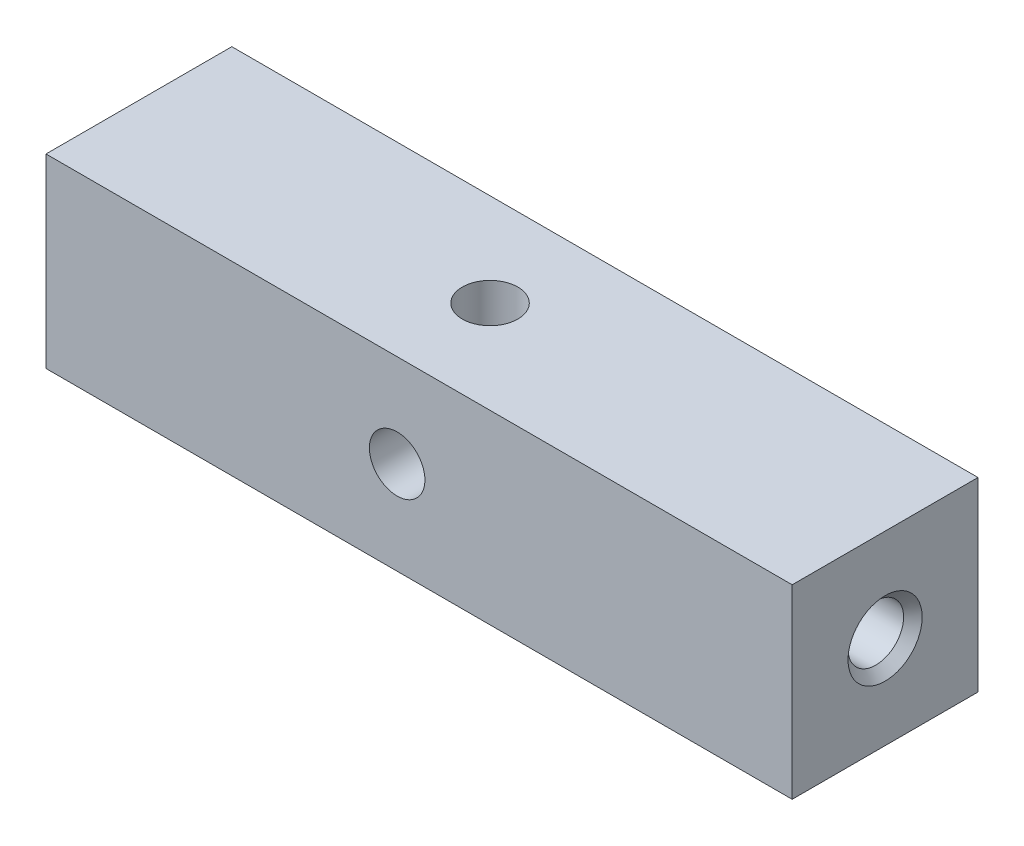
SolidWorks part; units mm, degrees
material "6061 Alloy"
ref_plane "Front Plane" through (0, 0, 0) normal (0, 0, 1) x (1, 0, 0)
ref_plane "Top Plane" through (0, 0, 0) normal (0, 1, 0) x (1, 0, 0)
ref_plane "Right Plane" through (0, 0, 0) normal (1, 0, 0) x (0, 0, -1)
sketch "Sketch1" plane through (0, 0, 0) normal (1, 0, 0) x (0, 0, -1)
  line L1 (6.35, -6.35) -> (-6.35, -6.35)
  line L2 (6.35, -6.35) -> (6.35, 6.35)
  line L3 (6.35, 6.35) -> (-6.35, 6.35)
  line L4 (-6.35, -6.35) -> (-6.35, 6.35)
  line L5 (6.35, -6.35) -> (-6.35, 6.35) construction
  line L6 (6.35, 6.35) -> (-6.35, -6.35) construction
  point P0 (0, 0)
  dimension "D1" = 12.7
  dimension "D2" = 12.7
extrude "Boss-Extrude1" add sketch "Sketch1" along normal blind 51
sketch "Sketch2" plane through (0, 0, 0) normal (-1, 0, 0) x (0, 0, 1)
  circle A0 centre (0, 0) radius 4.7625
  dimension "D1" = 9.525
sketch "Sketch9" plane through (51, 0, 0) normal (1, 0, 0) x (0, 0, -1)
  circle A0 centre (0, 0) radius 4.7625
  dimension "D1" = 9.525
hole_wizard "#10-24 Tapped Hole1" positions "Sketch12" profile "Sketch13" tap size "#10-24" standard "ANSI Inch" end condition through all
sketch "Sketch12" plane through (0, 0, 6.35) normal (0, 0, 1) x (1, 0, 0)
  line L0 (0, 6.35) -> (0, -6.35) construction
  point P0 (24, 0)
  dimension "D1" = 24
sketch "Sketch13" plane through (24, 0, 6.35) normal (1, 0, 0) x (0, -1, 0)
  line L0 (0, 0) -> (0, 12.7)
  line L1 (0, 12.7) -> (1.8986, 12.7)
  line L2 (1.8986, 12.7) -> (1.8986, 0)
  line L5 (1.8986, 0) -> (0, 0)
  line L11 (0, -6.35) -> (0, 107.95) construction
  dimension "Thru Tap Drill Dia." = 3.7973
  dimension "Thru Tap Drill Depth" = 12.7
cosmetic thread "Hole Thread1" parameters "D2"=4.826
hole_wizard "#10-24 Tapped Hole2" positions "Sketch14" profile "Sketch15" tap size "#10-24" standard "ANSI Inch" end condition through all
sketch "Sketch14" plane through (0, 6.35, 0) normal (0, 1, 0) x (1, 0, 0)
  line L0 (0, 6.35) -> (0, -6.35) construction
  point P0 (24, 0)
  dimension "D1" = 24
sketch "Sketch15" plane through (24, 6.35, 0) normal (1, 0, 0) x (0, 0, 1)
  line L0 (0, 0) -> (0, 12.7)
  line L1 (0, 12.7) -> (1.8986, 12.7)
  line L2 (1.8986, 12.7) -> (1.8986, 0)
  line L5 (1.8986, 0) -> (0, 0)
  line L11 (0, -6.35) -> (0, 107.95) construction
  dimension "Thru Tap Drill Dia." = 3.7973
  dimension "Thru Tap Drill Depth" = 12.7
cosmetic thread "Hole Thread2" parameters "D2"=4.826
hole_wizard "M6x1.0 Tapped Hole2" positions "Sketch18" profile "Sketch19" tap size "M6x1.0" standard "ANSI Metric"
sketch "Sketch18" plane through (0, 0, 0) normal (-1, 0, 0) x (0, 0, 1)
  point P0 (0, 0)
sketch "Sketch19" plane through (0, 0, 0) normal (0, 1, 0) x (0, 0, 1)
  line L0 (0, 0) -> (0, 21.8222)
  line L1 (0, 21.8222) -> (2.5, 20.32)
  line L2 (2.5, 20.32) -> (2.5, 0.525)
  line L3 (2.5, 0.525) -> (3.025, 0)
  line L5 (3.025, 0) -> (0, 0)
  line L6 (-2.5, 0.525) -> (-3.025, 0) construction
  line L10 (0, 21.8222) -> (-2.5, 20.32) construction
  line L11 (0, -6.35) -> (0, 107.95) construction
  dimension "Tap Drill Dia." = 5
  dimension "Tap Drill Depth" = 20.32
  dimension "Near C'Sink Dia." = 6.05
  dimension "Near C'Sink Angle" = 90
  dimension "Drill Angle" = 118
cosmetic thread "Hole Thread6" parameters "D1"=15.24, "D2"=6
hole_wizard "#10-24 Tapped Hole3" positions "Sketch20" profile "Sketch21" tap size "#10-24" standard "ANSI Inch"
sketch "Sketch20" plane through (51, 0, 0) normal (1, 0, 0) x (0, 0, -1)
  point P0 (0, 0)
sketch "Sketch21" plane through (51, 0, 0) normal (0, 1, 0) x (0, 0, -1)
  line L0 (0, 0) -> (0, 21.7148)
  line L1 (0, 21.7148) -> (1.8986, 20.574)
  line L2 (1.8986, 20.574) -> (1.8986, 0.635)
  line L3 (1.8986, 0.635) -> (2.5337, 0)
  line L5 (2.5337, 0) -> (0, 0)
  line L6 (-1.8986, 0.635) -> (-2.5337, 0) construction
  line L10 (0, 21.7148) -> (-1.8987, 20.574) construction
  line L11 (0, -6.35) -> (0, 107.95) construction
  dimension "Tap Drill Dia." = 3.7973
  dimension "Tap Drill Depth" = 20.574
  dimension "Near C'Sink Dia." = 5.0673
  dimension "Near C'Sink Angle" = 90
  dimension "Drill Angle" = 118
cosmetic thread "Hole Thread10" parameters "D1"=15.24, "D2"=6
